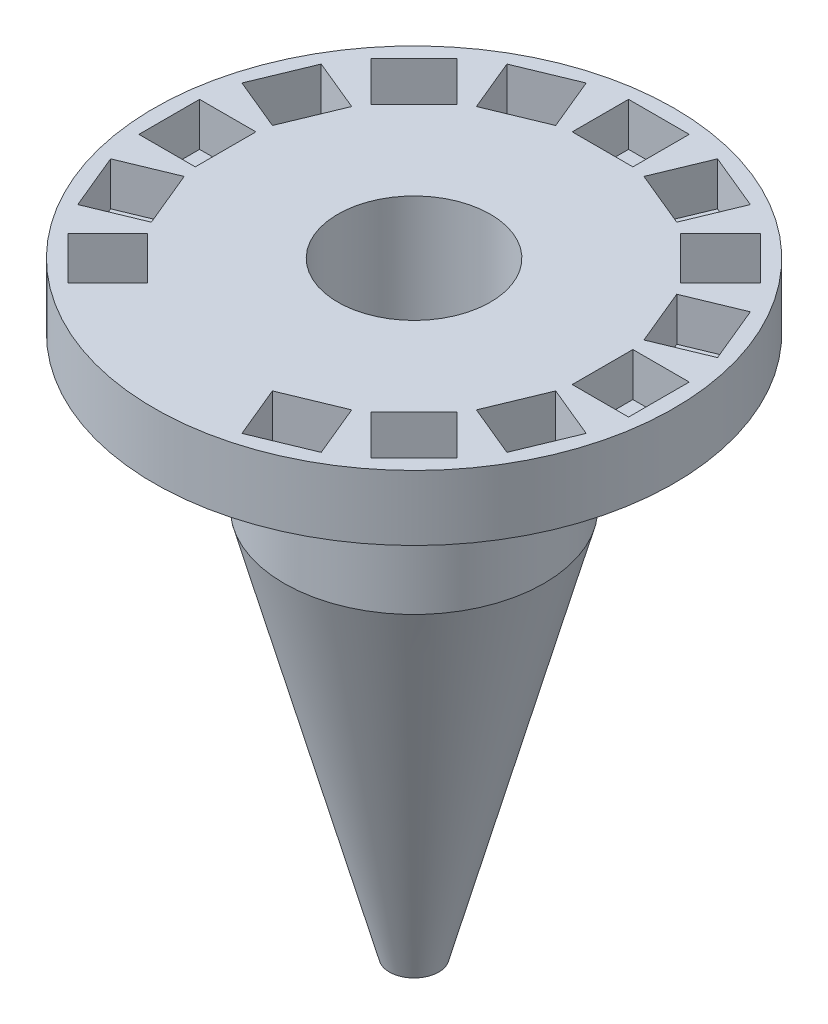
SolidWorks part; units mm, degrees
ref_plane "Front Plane" through (0, 0, 0) normal (0, 0, 1) x (1, 0, 0)
ref_plane "Top Plane" through (0, 0, 0) normal (0, 1, 0) x (1, 0, 0)
ref_plane "Right Plane" through (0, 0, 0) normal (1, 0, 0) x (0, 0, -1)
sketch "Sketch1" plane through (0, 0, 0) normal (1, 0, 0) x (0, 0, -1)
  line L0 (0, 0) -> (0, 8288.9361) construction
  line L1 (1.76, 2.5) -> (6, 2.5)
  line L2 (6, 2.5) -> (6, 1)
  line L3 (6, 1) -> (3, 1)
  line L4 (3, 1) -> (3, -2.5)
  line L6 (1.76, -2.5) -> (1.76, 2.5)
  line L7 (1.76, -2.5) -> (0.2957, -11.4829)
  line L8 (0.2957, -11.4829) -> (0.5705, -11.4829)
  line L9 (0.5705, -11.4829) -> (3, -2.5)
  point P5 (1.76, 0)
  dimension "D1" = 1.76
  dimension "D2" = 6
  dimension "D3" = 1.5
  dimension "D4" = 5
  dimension "D5" = 3
revolve "Revolve1" add sketch "Sketch1" angle 360 about L0
sketch "Sketch2" plane through (0, 2.5, 0) normal (0, 1, 0) x (1, 0, 0)
  line L1 (-0.7, 4.35) -> (0.7, 4.35)
  line L2 (-0.7, 4.35) -> (-0.7, 5.65)
  line L3 (-0.7, 5.65) -> (0.7, 5.65)
  line L4 (0.7, 4.35) -> (0.7, 5.65)
  line L5 (-0.7, 4.35) -> (0.7, 5.65) construction
  line L6 (-0.7, 5.65) -> (0.7, 4.35) construction
  point P0 (0, 5)
  point P5 (-2.2097, 3.1505)
  point P6 (0.6751, 3.5267)
  point P7 (0.2518, 3.9187)
  point P9 (0, 0)
  point P10 (-0.9241, 4)
  point P11 (0, 0)
  dimension "D1" = 1.4
  dimension "D2" = 1.3
  dimension "D3" = 5
extrude "Cut-Extrude1" cut sketch "Sketch2" against normal blind 1
pattern_circular "CirPattern1" count 16 over 360 about axis through (0, 0, 0) along (0, -1, 0) skipping 8, 9 of "Cut-Extrude1"
equation "\"Radius\"= 5"
equation "\"D3@Sketch2\"=\"Radius\""
